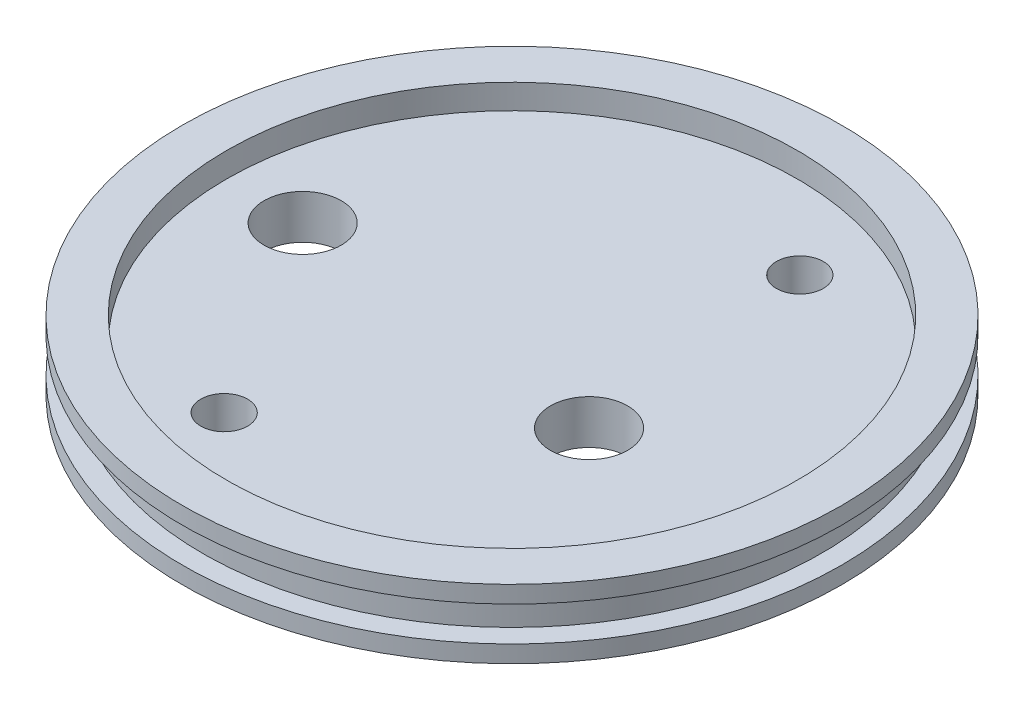
SolidWorks part; units mm, degrees
material "6061-T6 (SS)"
ref_plane "Front Plane" through (0, 0, 0) normal (0, 0, 1) x (1, 0, 0)
ref_plane "Top Plane" through (0, 0, 0) normal (0, 1, 0) x (1, 0, 0)
ref_plane "Right Plane" through (0, 0, 0) normal (1, 0, 0) x (0, 0, -1)
sketch "Sketch1" plane through (0, 0, 0) normal (0, 0, 1) x (1, 0, 0)
  line L0 (0, 48.1922) -> (0, -25.6743) construction
  line L1 (0, 0) -> (47.498, 0)
  line L2 (47.498, 0) -> (47.498, 2.4638)
  line L3 (47.498, 2.4638) -> (44.577, 2.4638)
  line L4 (44.577, 2.4638) -> (44.577, 7.4422)
  line L5 (44.577, 7.4422) -> (47.498, 7.4422)
  line L6 (47.498, 7.4422) -> (47.498, 9.906)
  line L7 (47.498, 9.906) -> (41.148, 9.906)
  line L8 (41.148, 9.906) -> (41.148, 6.35)
  line L9 (41.148, 6.35) -> (0, 6.35)
  line L10 (0, 6.35) -> (0, 0)
  dimension "D1" = 94.996
  dimension "D2" = 4.9784
  dimension "D3" = 2.921
  dimension "D4" = 9.906
  dimension "D5" = 6.35
  dimension "D6" = 6.35
revolve "Revolve1" add sketch "Sketch1" angle 360 about L0
hole_wizard "Pipe Tap Drill for 1/4 Tap1" positions "Sketch2" profile "Sketch3" hole size "1/4" standard "ANSI Inch" end condition through all
sketch "Sketch2" plane through (0, 6.35, 0) normal (0, 1, 0) x (1, 0, 0)
  point P0 (0, 0)
  point P3 (-30.1752, 0)
  dimension "D1" = 30.1752
sketch "Sketch3" plane through (0, 6.35, 0) normal (1, 0, 0) x (0, 0, 1)
  line L0 (0, 0) -> (0, 6.35)
  line L1 (0, 6.35) -> (5.5626, 6.35)
  line L2 (5.5626, 6.35) -> (5.5626, 0)
  line L5 (5.5626, 0) -> (0, 0)
  line L11 (0, -6.35) -> (0, 107.95) construction
  dimension "Thru Hole Dia." = 11.1252
  dimension "Thru Hole Depth" = 6.35
hole_wizard "1/4 Clearance Hole1" positions "Sketch4" profile "Sketch5" hole size "1/4" standard "ANSI Inch" end condition through all
sketch "Sketch4" plane through (0, 6.35, 0) normal (0, 1, 0) x (1, 0, 0)
  line L0 (0, 0) -> (-30.1752, 0)
  line L2 (0, 0) -> (12.1502, 29.3332)
  line L4 (0, 0) -> (-12.1502, -29.3332)
  point P0 (12.1502, 29.3332)
  point P2 (-12.1502, -29.3332)
  dimension "D1" = 31.75
  dimension "D2" = 112.5
sketch "Sketch5" plane through (12.1502, 6.35, -29.3332) normal (1, 0, 0) x (0, 0, 1)
  line L0 (0, 0) -> (0, 6.35)
  line L1 (0, 6.35) -> (3.3782, 6.35)
  line L2 (3.3782, 6.35) -> (3.3782, 0)
  line L5 (3.3782, 0) -> (0, 0)
  line L11 (0, -6.35) -> (0, 107.95) construction
  dimension "Thru Hole Dia." = 6.7564
  dimension "Thru Hole Depth" = 6.35
sketch "Sketch6" plane through (0, 0, 0) normal (0, -1, 0) x (1, 0, 0)
  circle A0 centre (-12.1502, 29.3332) radius 6.35
  circle A1 centre (12.1502, -29.3332) radius 6.35
  dimension "D1" = 12.7
extrude "Optional C-Bore" [suppressed] cut sketch "Sketch6" against normal blind 3.81
sketch "Sketch7" plane through (0, 6.35, 0) normal (0, 1, 0) x (1, 0, 0)
  circle A0 centre (0, 0) radius 11.1125
  dimension "D1" = 22.225
extrude "Boss-Extrude1" add sketch "Sketch7" against normal blind 6.35 contours A0
sketch "Sketch8" plane through (0, 6.35, 0) normal (0, 1, 0) x (1, 0, 0)
  point P0 (16.0739, -4.9699)
  point P2 (16.0739, -4.9699)
  point P5 (16.0739, -4.9699)
hole_wizard "Pipe Tap Drill for 1/4 Tap2" positions "Sketch8" profile "Sketch9" hole size "1/4" standard "ANSI Inch" end condition up to next
sketch "Sketch9" plane through (16.0739, 6.35, 4.9699) normal (1, 0, 0) x (0, 0, 1)
  line L0 (0, 0) -> (0, 6.35)
  line L1 (0, 6.35) -> (5.5626, 6.35)
  line L2 (5.5626, 6.35) -> (5.5626, 0)
  line L5 (5.5626, 0) -> (0, 0)
  line L11 (0, -6.35) -> (0, 107.95) construction
  dimension "Thru Hole Dia." = 11.1252
  dimension "Thru Hole Depth" = 6.35
